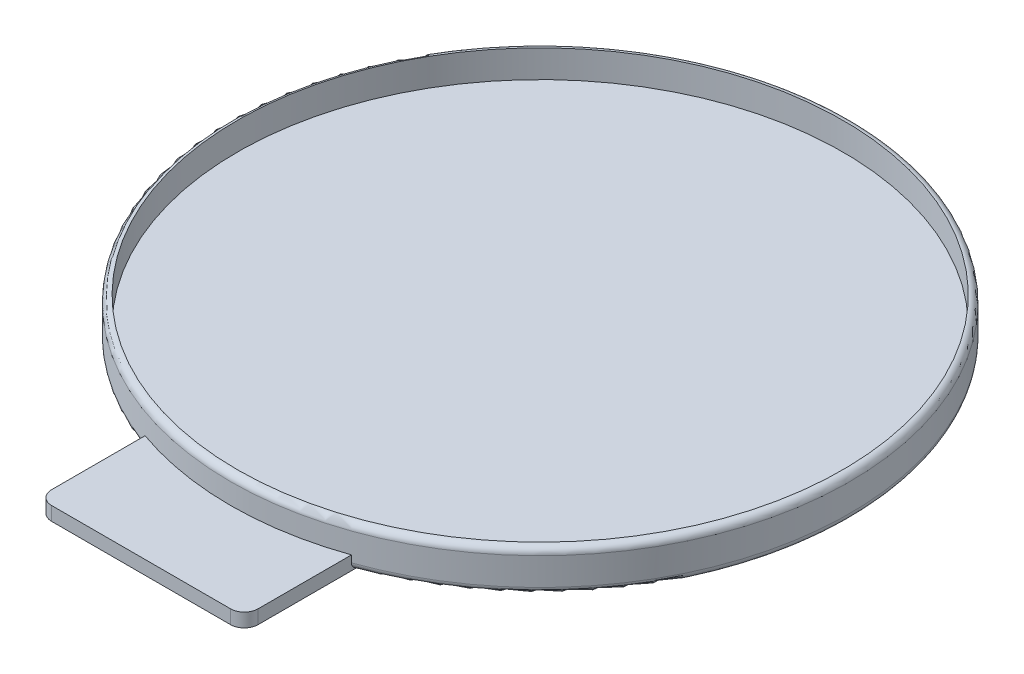
SolidWorks part; units mm, degrees
ref_plane "Front Plane" through (0, 0, 0) normal (0, 0, 1) x (1, 0, 0)
ref_plane "Top Plane" through (0, 0, 0) normal (0, 1, 0) x (1, 0, 0)
ref_plane "Right Plane" through (0, 0, 0) normal (1, 0, 0) x (0, 0, -1)
sketch "Sketch1" plane through (0, 0, 0) normal (0, 1, 0) x (1, 0, 0)
  circle A0 centre (0, 0) radius 225
  dimension "D1" = 450
extrude "Boss-Extrude1" add sketch "Sketch1" along normal blind 30
sketch "Sketch2" plane through (0, 30, 0) normal (0, 1, 0) x (1, 0, 0)
  circle A0 centre (0, 0) radius 220
  dimension "D1" = 440
extrude "Cut-Extrude1" cut sketch "Sketch2" against normal blind 20
sketch "Sketch3" plane through (0, 30, 0) normal (0, 1, 0) x (1, 0, 0)
  line L0 (-328.8798, 0) -> (285.674, 0) construction
  line L1 (0, 225) -> (0, -239.2439) construction
  line L3 (-300, 75) -> (-150, 75)
  line L4 (-300, 75) -> (-300, -75)
  line L5 (-300, -75) -> (-150, -75)
  line L6 (-150, 75) -> (-150, -75)
  line L7 (-300, 75) -> (-150, -75) construction
  line L8 (-300, -75) -> (-150, 75) construction
  circle A0 centre (0, 0) radius 225 construction
  point P8 (-225, 0)
  dimension "D1" = 150
  dimension "D2" = 150
extrude "Boss-Extrude2" [suppressed] add sketch "Sketch3" against normal blind 30
sketch "Sketch4" plane through (0, 0, 0) normal (0, 0, 1) x (1, 0, 0)
  line L0 (0, 0) -> (0, 177.4467) construction
  line L1 (-225, 0) -> (225, 0) construction
  line L3 (-75, 10) -> (75, 10)
  line L4 (-75, 10) -> (-75, 0)
  line L5 (-75, 0) -> (75, 0)
  line L6 (75, 10) -> (75, 0)
  line L7 (-75, 10) -> (75, 0) construction
  line L8 (-75, 0) -> (75, 10) construction
  point P4 (0, 5)
  dimension "D1" = 10
  dimension "D2" = 10
  dimension "D3" = 150
extrude "Boss-Extrude3" add sketch "Sketch4" along normal blind 290
fillet "Fillet1" radius 10 2 edges at (75, 5, 290) (-75, 5, 290)
fillet "Fillet2" radius 5 2 edges at (0, 0, -225) (0, 30, 225)
